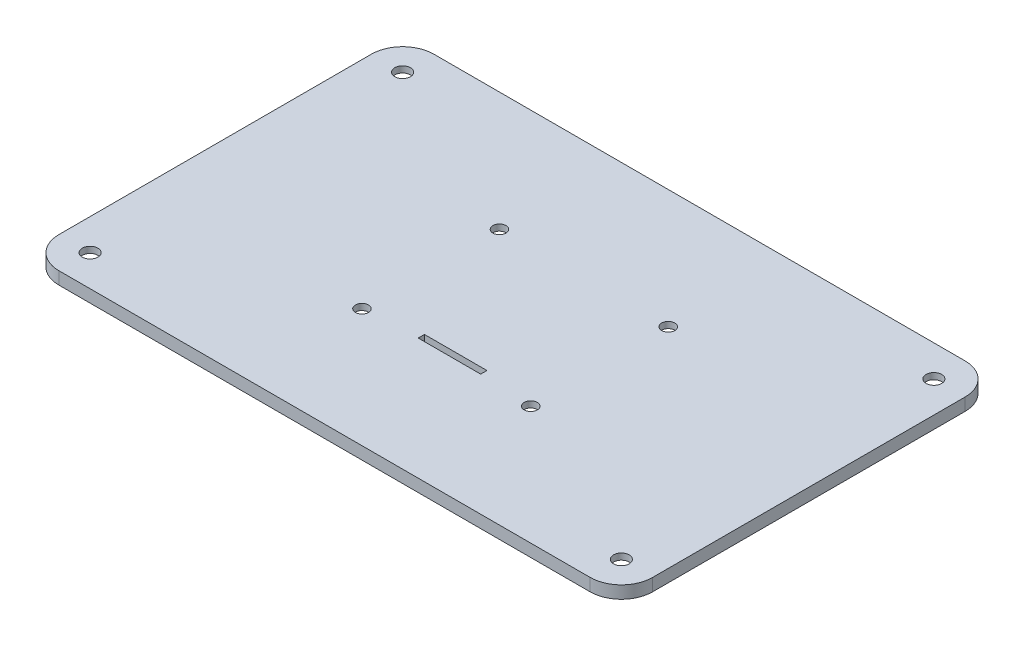
SolidWorks part; units mm, degrees
ref_plane "Front Plane" through (0, 0, 0) normal (0, 0, 1) x (1, 0, 0)
ref_plane "Top Plane" through (0, 0, 0) normal (0, 1, 0) x (1, 0, 0)
ref_plane "Right Plane" through (0, 0, 0) normal (1, 0, 0) x (0, 0, -1)
sketch "Sketch1" plane through (0, 111.7224, 0) normal (0, 1, 0) x (1, 0, 0)
  line L0 (249.4511, 952.2183) -> (249.4511, 944.7183)
  line L1 (241.9511, 959.7183) -> (234.4511, 959.7183)
  line L2 (404.4511, 952.2183) -> (404.4511, 944.7183)
  line L3 (411.9511, 959.7183) -> (419.4511, 959.7183)
  line L4 (241.9511, 942.2183) -> (411.9511, 942.2183)
  line L5 (421.9511, 952.2183) -> (421.9511, 1052.2183)
  line L6 (411.9511, 1062.2183) -> (241.9511, 1062.2183)
  line L7 (231.9511, 1052.2183) -> (231.9511, 952.2183)
  line L8 (241.9511, 942.2183) -> (411.9511, 942.2183)
  line L9 (421.9511, 952.2183) -> (421.9511, 1052.2183)
  line L10 (411.9511, 1062.2183) -> (241.9511, 1062.2183)
  line L11 (231.9511, 1052.2183) -> (231.9511, 952.2183)
  line L12 (249.4511, 944.7183) -> (404.4511, 944.7183)
  line L17 (419.4511, 959.7183) -> (419.4511, 1044.7183)
  line L18 (404.4511, 1059.7183) -> (249.4511, 1059.7183)
  line L19 (234.4511, 1044.7183) -> (234.4511, 959.7183)
  line L20 (411.9511, 1044.7183) -> (419.4511, 1044.7183)
  line L22 (326.9511, 942.2183) -> (326.9511, 1097.1265) construction
  line L23 (231.9511, 1002.2183) -> (434.7036, 1002.2183) construction
  line L26 (404.4511, 1052.2183) -> (404.4511, 1059.7183)
  line L27 (241.9511, 1044.7183) -> (234.4511, 1044.7183)
  line L28 (249.4511, 1052.2183) -> (249.4511, 1059.7183)
  line L29 (234.4511, 1052.2183) -> (234.4511, 952.2183) construction
  line L30 (411.9511, 1059.7183) -> (241.9511, 1059.7183) construction
  line L31 (241.9511, 944.7183) -> (411.9511, 944.7183) construction
  line L32 (419.4511, 952.2183) -> (419.4511, 1052.2183) construction
  arc A4 (411.9511, 942.2183) -> (421.9511, 952.2183) centre (411.9511, 952.2183) ccw
  arc A5 (421.9511, 1052.2183) -> (411.9511, 1062.2183) centre (411.9511, 1052.2183) ccw
  arc A6 (241.9511, 1062.2183) -> (231.9511, 1052.2183) centre (241.9511, 1052.2183) ccw
  arc A7 (231.9511, 952.2183) -> (241.9511, 942.2183) centre (241.9511, 952.2183) ccw
  arc A8 (411.9511, 942.2183) -> (421.9511, 952.2183) centre (411.9511, 952.2183) ccw
  arc A9 (421.9511, 1052.2183) -> (411.9511, 1062.2183) centre (411.9511, 1052.2183) ccw
  arc A10 (241.9511, 1062.2183) -> (231.9511, 1052.2183) centre (241.9511, 1052.2183) ccw
  arc A11 (231.9511, 952.2183) -> (241.9511, 942.2183) centre (241.9511, 952.2183) ccw
  circle A16 centre (241.9511, 952.2183) radius 5.5
  circle A17 centre (411.9511, 952.2183) radius 5.5
  circle A18 centre (411.9511, 1052.2183) radius 5.5
  circle A19 centre (241.9511, 1052.2183) radius 5.5
  arc A20 (249.4511, 952.2183) -> (241.9511, 959.7183) centre (241.9511, 952.2183) ccw
  arc A21 (411.9511, 959.7183) -> (404.4511, 952.2183) centre (411.9511, 952.2183) ccw
  arc A22 (404.4511, 1052.2183) -> (411.9511, 1044.7183) centre (411.9511, 1052.2183) ccw
  arc A23 (241.9511, 1044.7183) -> (249.4511, 1052.2183) centre (241.9511, 1052.2183) ccw
  arc A24 (241.9511, 1059.7183) -> (234.4511, 1052.2183) centre (241.9511, 1052.2183) ccw construction
  arc A25 (234.4511, 952.2183) -> (241.9511, 944.7183) centre (241.9511, 952.2183) ccw construction
  arc A26 (419.4511, 1052.2183) -> (411.9511, 1059.7183) centre (411.9511, 1052.2183) ccw construction
  arc A27 (411.9511, 944.7183) -> (419.4511, 952.2183) centre (411.9511, 952.2183) ccw construction
  dimension "D2" = 2.5
  dimension "D3" = 11
  dimension "D1" = 0
extrude "Boss-Extrude1" add sketch "Sketch1" along normal up to surface (5 mm away) region at (246.1217, 111.7224, -956.389) region at (407.7804, 111.7224, -956.389) region at (246.1217, 111.7224, -1048.0476) region at (407.7804, 111.7224, -1048.0476) region at (236.469, 111.7224, -946.7362)
sketch "Sketch2" plane through (0, 116.7224, 0) normal (0, 1, 0) x (1, 0, 0)
  line L4 (231.9511, 1052.2183) -> (231.9511, 952.2183)
  line L5 (241.9511, 942.2183) -> (411.9511, 942.2183)
  line L6 (421.9511, 952.2183) -> (421.9511, 1052.2183)
  line L7 (411.9511, 1062.2183) -> (241.9511, 1062.2183)
  line L8 (231.9511, 1052.2183) -> (231.9511, 952.2183)
  line L9 (241.9511, 942.2183) -> (411.9511, 942.2183)
  line L10 (421.9511, 952.2183) -> (421.9511, 1052.2183)
  line L11 (411.9511, 1062.2183) -> (241.9511, 1062.2183)
  arc A4 (231.9511, 952.2183) -> (241.9511, 942.2183) centre (241.9511, 952.2183) ccw
  arc A5 (411.9511, 942.2183) -> (421.9511, 952.2183) centre (411.9511, 952.2183) ccw
  arc A6 (421.9511, 1052.2183) -> (411.9511, 1062.2183) centre (411.9511, 1052.2183) ccw
  arc A7 (241.9511, 1062.2183) -> (231.9511, 1052.2183) centre (241.9511, 1052.2183) ccw
  arc A8 (231.9511, 952.2183) -> (241.9511, 942.2183) centre (241.9511, 952.2183) ccw
  arc A9 (411.9511, 942.2183) -> (421.9511, 952.2183) centre (411.9511, 952.2183) ccw
  arc A10 (421.9511, 1052.2183) -> (411.9511, 1062.2183) centre (411.9511, 1052.2183) ccw
  arc A11 (241.9511, 1062.2183) -> (231.9511, 1052.2183) centre (241.9511, 1052.2183) ccw
  dimension "D1" = 0
extrude "Boss-Extrude2" add sketch "Sketch2" along normal blind 2
sketch "Sketch4" plane through (0, 118.7224, 0) normal (0, 1, 0) x (1, 0, 0)
  line L1 (375.8652, 1031.6724) -> (399.8652, 1031.6724)
  line L2 (375.8652, 1031.6724) -> (375.8652, 1007.6724)
  line L3 (375.8652, 1007.6724) -> (399.8652, 1007.6724)
  line L4 (399.8652, 1031.6724) -> (399.8652, 1007.6724)
  circle A0 centre (375.8652, 1031.6724) radius 1.4
  circle A1 centre (399.8652, 1031.6724) radius 1.4
  circle A4 centre (375.8652, 1007.6724) radius 1.4
  circle A5 centre (399.8652, 1007.6724) radius 1.4
  dimension "D3" = 2.8
  dimension "D1" = 24
  dimension "D2" = 24
extrude "Boss-Extrude3" add sketch "Sketch4" against normal blind 7 contours L1 A0 L2 | L2 A0 L1 | L2 A4 L3 | L3 A4 L2 | A1 | A5 region at (375.6672, 118.7224, -1031.8705) region at (376.4594, 118.7224, -1031.0782) region at (376.4594, 118.7224, -1008.2666) region at (375.6672, 118.7224, -1007.4744)
sketch "Sketch10" plane through (0, 118.7224, 0) normal (0, 1, 0) x (1, 0, 0)
  line L0 (231.9511, 1002.2183) -> (421.9511, 1002.2183) construction
  line L1 (231.9511, 1052.2183) -> (231.9511, 952.2183) construction
  line L2 (421.9511, 952.2183) -> (421.9511, 1052.2183) construction
  line L3 (326.9511, 1062.2183) -> (326.9511, 942.2183) construction
  line L4 (411.9511, 1062.2183) -> (241.9511, 1062.2183) construction
  line L5 (241.9511, 942.2183) -> (411.9511, 942.2183) construction
sketch "Sketch12" plane through (0, 118.7224, 0) normal (0, 1, 0) x (1, 0, 0)
  line L0 (326.9511, 1062.2183) -> (326.9511, 942.2183) construction
  line L1 (318.1088, 983.0453) -> (338.1088, 983.0453)
  line L2 (318.1088, 983.0453) -> (318.1088, 981.0453)
  line L3 (318.1088, 981.0453) -> (338.1088, 981.0453)
  line L4 (338.1088, 983.0453) -> (338.1088, 981.0453)
  line L5 (411.9511, 1062.2183) -> (241.9511, 1062.2183) construction
  line L6 (241.9511, 942.2183) -> (411.9511, 942.2183) construction
extrude "Cut-Extrude1" cut sketch "Sketch12" against normal blind 10
hole_wizard "Ø4.2 (4.2) Diameter Hole1" positions "Sketch13" profile "Sketch14" hole size "Ø4.2" standard "ISO"
sketch "Sketch13" plane through (0, 118.7224, 0) normal (0, 1, 0) x (1, 0, 0)
  point P0 (300.991, 1024.1708)
  point P3 (354.991, 1024.1708)
  point P6 (354.991, 980.1708)
  point P9 (300.991, 980.1708)
sketch "Sketch14" plane through (300.991, 118.7224, -1024.1708) normal (1, 0, 0) x (0, 0, 1)
  line L0 (0, 0) -> (0, 21.2618)
  line L1 (0, 21.2618) -> (2.1, 20)
  line L2 (2.1, 20) -> (2.1, 0)
  line L5 (2.1, 0) -> (0, 0)
  line L10 (0, 21.2618) -> (-2.1, 20) construction
  line L11 (0, -6.35) -> (0, 107.95) construction
  dimension "Hole Dia." = 4.2
  dimension "Hole Depth" = 20
  dimension "Drill Angle" = 118
hole_wizard "Ø5.0 (5) Diameter Hole1" positions "Sketch18" profile "Sketch19" hole size "Ø5.0" standard "ISO"
sketch "Sketch18" plane through (0, 118.7224, 0) normal (0, 1, 0) x (1, 0, 0)
  point P3 (241.9511, 1052.2183)
  point P6 (411.9511, 1052.2183)
  point P9 (411.9511, 952.2183)
  point P12 (241.9511, 952.2183)
sketch "Sketch19" plane through (241.9511, 118.7224, -1052.2183) normal (1, 0, 0) x (0, 0, 1)
  line L0 (0, 0) -> (0, 6.5022)
  line L1 (0, 6.5022) -> (2.5, 5)
  line L2 (2.5, 5) -> (2.5, 0)
  line L5 (2.5, 0) -> (0, 0)
  line L10 (0, 6.5022) -> (-2.5, 5) construction
  line L11 (0, -6.35) -> (0, 107.95) construction
  dimension "Hole Dia." = 5
  dimension "Hole Depth" = 5
  dimension "Drill Angle" = 118
extrude "Cut-Extrude2" cut sketch "Sketch1<3>" along normal blind 3
sketch "Sketch1<3>" plane through (0, 111.7224, 0) normal (0, 1, 0) x (1, 0, 0) same geometry as "Sketch1"
